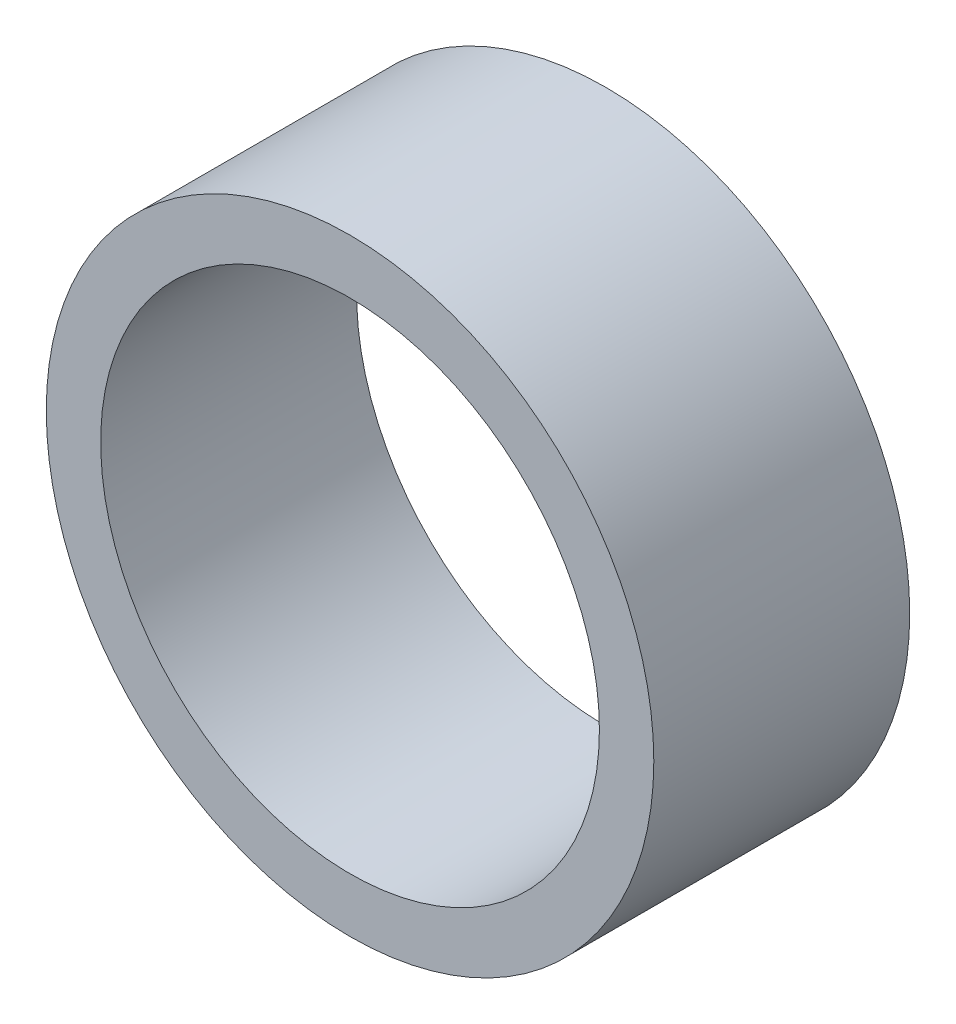
SolidWorks part; units mm, degrees
ref_plane "Front Plane" through (0, 0, 0) normal (0, 0, 1) x (1, 0, 0)
ref_plane "Top Plane" through (0, 0, 0) normal (0, 1, 0) x (1, 0, 0)
ref_plane "Right Plane" through (0, 0, 0) normal (1, 0, 0) x (0, 0, -1)
sketch "Sketch1" plane through (0, 0, 0) normal (0, 0, 1) x (1, 0, 0)
  circle A0 centre (0, 0) radius 24.75
  circle A1 centre (0, 0) radius 30.15
  dimension "Out_dia" = 60.3
  dimension "Thickness" = 5.4
extrude "BaseSection" add sketch "Sketch1" along normal mid plane 25.4
